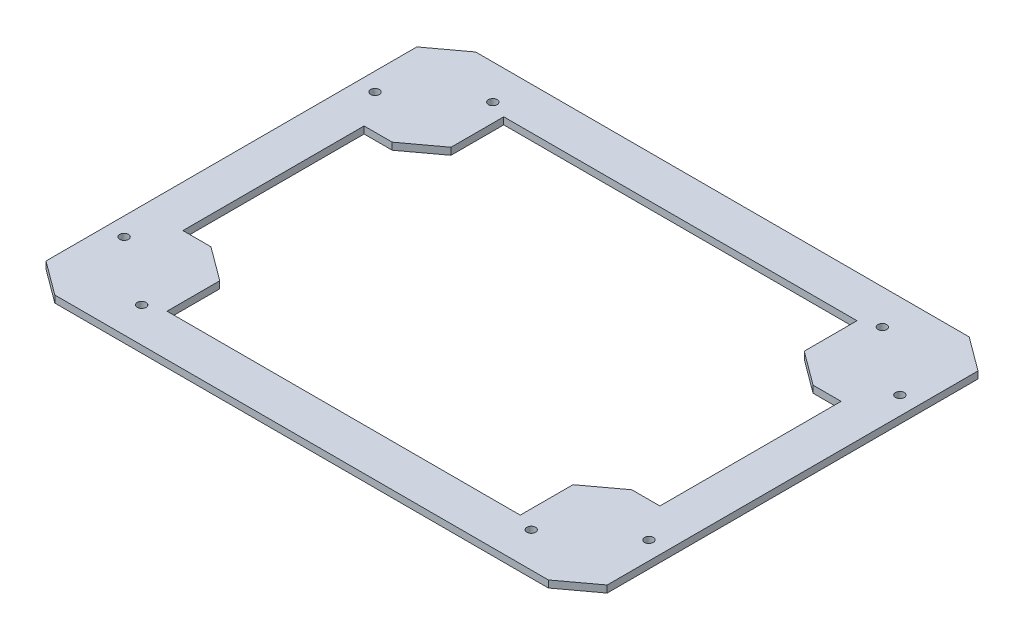
SolidWorks part; units mm, degrees
material "Thornel Mat VMA"
ref_plane "Front Plane" through (0, 0, 0) normal (0, 0, 1) x (1, 0, 0)
ref_plane "Top Plane" through (0, 0, 0) normal (0, 1, 0) x (1, 0, 0)
ref_plane "Right Plane" through (0, 0, 0) normal (1, 0, 0) x (0, 0, -1)
sketch "Sketch1" plane through (0, 0, 0) normal (0, 1, 0) x (1, 0, 0)
  line L0 (-127, 83.9186) -> (-111.6865, 95.25)
  line L1 (-127, -95.25) -> (127, -95.25)
  line L2 (-127, -95.25) -> (-127, 95.25)
  line L3 (-127, 95.25) -> (127, 95.25)
  line L4 (127, -95.25) -> (127, 95.25)
  line L5 (-107.95, 41.011) -> (-107.95, -41.011)
  line L8 (-107.95, 41.011) -> (-95.25, 41.011)
  line L10 (-127, 95.25) -> (127, -95.25) construction
  line L12 (127, 83.9186) -> (111.6865, 95.25)
  line L14 (79.9365, 52.3423) -> (79.9365, 76.2)
  line L15 (95.25, 41.011) -> (79.9365, 52.3423)
  line L16 (107.95, 41.011) -> (95.25, 41.011)
  line L17 (107.95, 41.011) -> (107.95, -41.011)
  line L18 (127, -83.9186) -> (111.6865, -95.25)
  line L19 (107.95, -41.011) -> (95.25, -41.011)
  line L20 (95.25, -41.011) -> (79.9365, -52.3423)
  line L21 (79.9365, -52.3423) -> (79.9365, -76.2)
  line L22 (127, 0) -> (-127, 0) construction
  line L23 (0, -13.6985) -> (0, 95.25) construction
  line L26 (-79.9365, -52.3423) -> (-79.9365, -76.2)
  line L27 (-95.25, 41.011) -> (-127, 83.9186) construction
  line L28 (-95.25, 41.011) -> (-79.9365, 52.3423)
  line L29 (-79.9365, 52.3423) -> (-79.9365, 76.2)
  line L31 (-95.25, -41.011) -> (-79.9365, -52.3423)
  line L32 (-107.95, -41.011) -> (-95.25, -41.011)
  line L33 (-127, -83.9186) -> (-111.6865, -95.25)
  line L34 (-79.9365, 52.3423) -> (-111.6865, 95.25) construction
  line L36 (-79.9365, 76.2) -> (79.9365, 76.2)
  line L37 (38.8318, 76.2) -> (79.9365, 76.2)
  line L38 (-79.9365, -76.2) -> (79.9365, -76.2)
  line L39 (38.1, -76.2) -> (79.9365, -76.2)
  point P0 (0, 0)
  point P1 (0, 0)
  point P14 (0, 0)
  point P22 (0, 76.2)
  point P33 (107.95, 0)
  point P41 (0, 0)
  point P44 (-107.95, 0)
  point P45 (-38.1, 0)
  point P46 (-31.75, 0)
  dimension "D1" = 190.5
  dimension "D2" = 254
  dimension "D3" = 19.05
  dimension "D4" = 19.05
  dimension "D5" = 143.5
  dimension "D6" = 19.05
  dimension "D7" = 12.7
extrude "Boss-Extrude1" add sketch "Sketch1" along normal blind 3.175 contours L2 L1 L4 L3 L8 region at (-117.4547, 0, -87.0321)
sketch "Sketch2" plane through (0, 3.175, 0) normal (0, 1, 0) x (1, 0, 0)
  line L0 (-87.5933, 46.6767) -> (-119.3433, 89.5843) construction
  line L1 (-95.25, 41.011) -> (-79.9365, 52.3423) construction
  line L2 (-127, 83.9186) -> (-111.6865, 95.25) construction
  line L3 (0, 0) -> (0, 95.25) construction
  line L4 (-111.6865, 95.25) -> (111.6865, 95.25) construction
  line L5 (0, 0) -> (-127, 0) construction
  line L6 (-127, -83.9186) -> (-127, 83.9186) construction
  line L7 (-103.4683, 68.1305) -> (-88.1548, 79.4619) construction
  circle A0 centre (-88.1548, 79.4619) radius 1.9844
  circle A1 centre (88.1548, 79.4619) radius 1.9844
  circle A2 centre (88.1548, -79.4619) radius 1.9844
  circle A3 centre (-88.1548, -79.4619) radius 1.9844
  circle A4 centre (-118.7817, 56.7991) radius 1.9844
  circle A5 centre (118.7817, 56.7991) radius 1.9844
  circle A6 centre (-118.7817, -56.7991) radius 1.9844
  circle A7 centre (118.7817, -56.7991) radius 1.9844
  dimension "D2" = 3.9688
  dimension "D1" = 19.05
extrude "Cut-Extrude1" cut sketch "Sketch2" against normal through all
